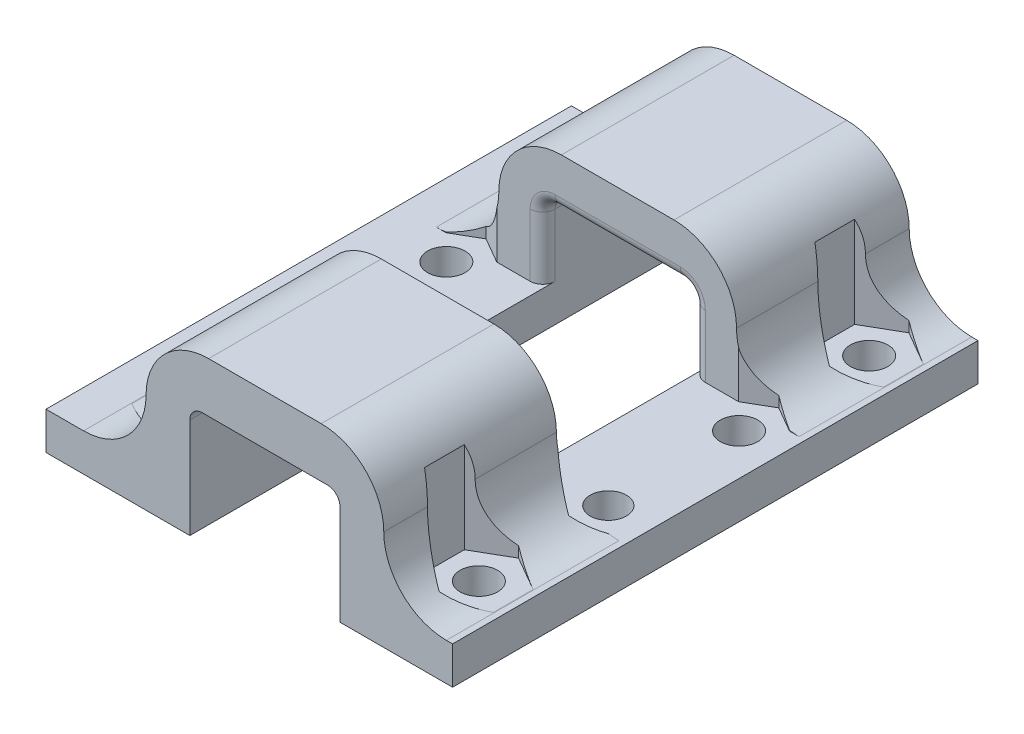
SolidWorks part; units mm, degrees
ref_plane "Спереди" through (0, 0, 0) normal (0, 0, 1) x (1, 0, 0)
ref_plane "Сверху" through (0, 0, 0) normal (0, 1, 0) x (1, 0, 0)
ref_plane "Справа" through (0, 0, 0) normal (1, 0, 0) x (0, 0, -1)
sketch "Эскиз2" plane through (0, 0, 0) normal (0, 1, 0) x (1, 0, 0)
  line L0 (-16.25, -21) -> (16.25, -21)
  line L1 (-16.25, -21) -> (-16.25, 21)
  line L2 (-16.25, 21) -> (16.25, 21)
  line L3 (16.25, -21) -> (16.25, 21)
  circle A0 centre (-10.45, -15.6) radius 1.5
  circle A1 centre (-10.45, -5.2) radius 1.5
  circle A2 centre (-10.45, 5.2) radius 1.5
  circle A3 centre (-10.45, 15.6) radius 1.5
  circle A4 centre (12.95, 15.6) radius 1.5
  circle A5 centre (12.95, 5.2) radius 1.5
  circle A6 centre (12.8998, -5.2) radius 1.4498
  circle A7 centre (12.95, -15.6) radius 1.5
extrude "Бобышка-Вытянуть1" add sketch "Эскиз2" along normal blind 3
sketch "Эскиз4" plane through (0, 3, 0) normal (0, 1, 0) x (1, 0, 0)
  line L0 (-10.45, 15.6) -> (12.95, 15.6) construction
  line L1 (1.25, 15.6) -> (1.25, -15.6) construction
  line L3 (-10.45, -15.6) -> (12.95, -15.6) construction
  line L4 (-16.25, -21) -> (16.25, -21) construction
  line L5 (-4.75, 21) -> (7.25, 21)
  line L6 (-4.75, 21) -> (-4.75, -21)
  line L7 (-4.75, -21) -> (7.25, -21)
  line L8 (7.25, 21) -> (7.25, -21)
  line L9 (-4.75, 21) -> (7.25, -21) construction
  line L10 (-4.75, -21) -> (7.25, 21) construction
  circle A0 centre (12.95, -15.6) radius 1.5 construction
  point P5 (1.25, 0)
  point P16 (11.45, -15.6)
  dimension "D1" = 12
extrude "Вырез-Вытянуть1" cut sketch "Эскиз4" against normal blind 22 contours L6 L5 L8 L7
sketch "Эскиз5" plane through (0, 0, 21) normal (0, 0, 1) x (1, 0, 0)
  line L0 (-16.25, 0) -> (-4.75, 0) construction
  line L2 (-4.75, 0) -> (-4.75, 3)
  line L4 (7.25, 0) -> (7.25, 3)
  line L6 (-4.75, 3) -> (-4.75, 9)
  line L7 (-4.75, 9) -> (7.25, 9)
  line L8 (7.25, 3) -> (7.25, 9)
  line L9 (-8.25, 0) -> (-4.75, 0)
  line L10 (-8.25, 0) -> (-8.25, 13)
  line L11 (-8.25, 13) -> (10.75, 13)
  line L12 (10.75, 0) -> (10.75, 13)
  line L13 (7.25, 0) -> (10.75, 0)
  dimension "D2" = 3.5
  dimension "D3" = 3.5
  dimension "D4" = 4
extrude "Бобышка-Вытянуть2" add sketch "Эскиз5" against normal up to surface (42 mm away) up to face at (11.75, 1.5, -21)
fillet "Скругление1" radius 5 4 edges at (-8.25, 13, 0) (10.75, 13, 0) (-8.25, 3, 0) (10.75, 3, 0)
sketch "Эскиз6" plane through (0, 13, 0) normal (0, 1, 0) x (1, 0, 0)
  line L0 (-3.25, 0) -> (5.75, 0) construction
  line L1 (-3.25, 21) -> (-3.25, -21) construction
  line L2 (5.75, -21) -> (5.75, 21) construction
  line L4 (-18.2884, -7.2) -> (18.2884, -7.2)
  line L5 (-18.2884, -7.2) -> (-18.2884, 7.2)
  line L6 (-18.2884, 7.2) -> (18.2884, 7.2)
  line L7 (18.2884, -7.2) -> (18.2884, 7.2)
  line L8 (-18.2884, -7.2) -> (18.2884, 7.2) construction
  line L9 (-18.2884, 7.2) -> (18.2884, -7.2) construction
  circle A0 centre (12.8998, -5.2) radius 1.4498 construction
  point P6 (0, 0)
  dimension "D1" = 2
extrude "Вырез-Вытянуть2" cut sketch "Эскиз6" against normal up to surface (10 mm away) up to face at (16, 3, 0)
fillet "Скругление2" radius 1 10 edges at (7.25, 6, 7.2) (7.25, 6, -7.2) (1.25, 9, 7.2) (1.25, 9, -7.2) (-4.75, 6, 7.2) (-4.75, 6, -7.2) (-4.75, 9, -14.1) (7.25, 9, -14.1) (7.25, 9, 14.1) (-4.75, 9, 14.1)
sketch "Эскиз7" plane through (0, 13, 0) normal (0, 1, 0) x (1, 0, 0)
  line L1 (-10.45, -12.4246) -> (-13.2, -14.0123)
  line L2 (-13.2, -14.0123) -> (-13.2, -17.1877)
  line L3 (-13.2, -17.1877) -> (-10.45, -18.7754)
  line L4 (-10.45, -18.7754) -> (-7.7, -17.1877)
  line L5 (-7.7, -17.1877) -> (-7.7, -14.0123)
  line L6 (-7.7, -14.0123) -> (-10.45, -12.4246)
  line L7 (12.95, -12.4246) -> (10.2, -14.0123)
  line L8 (10.2, -14.0123) -> (10.2, -17.1877)
  line L9 (10.2, -17.1877) -> (12.95, -18.7754)
  line L10 (12.95, -18.7754) -> (15.7, -17.1877)
  line L11 (15.7, -17.1877) -> (15.7, -14.0123)
  line L12 (15.7, -14.0123) -> (12.95, -12.4246)
  line L13 (-10.45, -8.3754) -> (-7.7, -6.7877)
  line L14 (-7.7, -6.7877) -> (-7.7, -3.6123)
  line L15 (-7.7, -3.6123) -> (-10.45, -2.0246)
  line L16 (-10.45, -2.0246) -> (-13.2, -3.6123)
  line L17 (-13.2, -3.6123) -> (-13.2, -6.7877)
  line L18 (-13.2, -6.7877) -> (-10.45, -8.3754)
  line L19 (-10.45, 2.0246) -> (-7.7, 3.6123)
  line L20 (-7.7, 3.6123) -> (-7.7, 6.7877)
  line L21 (-7.7, 6.7877) -> (-10.45, 8.3754)
  line L22 (-10.45, 8.3754) -> (-13.2, 6.7877)
  line L23 (-13.2, 6.7877) -> (-13.2, 3.6123)
  line L24 (-13.2, 3.6123) -> (-10.45, 2.0246)
  line L25 (-10.45, 12.4246) -> (-7.7, 14.0123)
  line L26 (-7.7, 14.0123) -> (-7.7, 17.1877)
  line L27 (-7.7, 17.1877) -> (-10.45, 18.7754)
  line L28 (-10.45, 18.7754) -> (-13.2, 17.1877)
  line L29 (-13.2, 17.1877) -> (-13.2, 14.0123)
  line L30 (-13.2, 14.0123) -> (-10.45, 12.4246)
  line L31 (12.8998, -8.3754) -> (15.6498, -6.7877)
  line L32 (15.6498, -6.7877) -> (15.6498, -3.6123)
  line L33 (15.6498, -3.6123) -> (12.8998, -2.0246)
  line L34 (12.8998, -2.0246) -> (10.1498, -3.6123)
  line L35 (10.1498, -3.6123) -> (10.1498, -6.7877)
  line L36 (10.1498, -6.7877) -> (12.8998, -8.3754)
  line L37 (12.95, 2.0246) -> (15.7, 3.6123)
  line L38 (15.7, 3.6123) -> (15.7, 6.7877)
  line L39 (15.7, 6.7877) -> (12.95, 8.3754)
  line L40 (12.95, 8.3754) -> (10.2, 6.7877)
  line L41 (10.2, 6.7877) -> (10.2, 3.6123)
  line L42 (10.2, 3.6123) -> (12.95, 2.0246)
  line L43 (12.95, 12.4246) -> (15.7, 14.0123)
  line L44 (15.7, 14.0123) -> (15.7, 17.1877)
  line L45 (15.7, 17.1877) -> (12.95, 18.7754)
  line L46 (12.95, 18.7754) -> (10.2, 17.1877)
  line L47 (10.2, 17.1877) -> (10.2, 14.0123)
  line L48 (10.2, 14.0123) -> (12.95, 12.4246)
  circle A0 centre (-10.45, -15.6) radius 2.75 construction
  circle A1 centre (12.95, -15.6) radius 2.75 construction
  circle A2 centre (-10.45, -5.2) radius 2.75 construction
  circle A3 centre (-10.45, 5.2) radius 2.75 construction
  circle A4 centre (-10.45, 15.6) radius 2.75 construction
  circle A5 centre (12.8998, -5.2) radius 2.75 construction
  circle A6 centre (12.95, 5.2) radius 2.75 construction
  circle A7 centre (12.95, 15.6) radius 2.75 construction
  dimension "D1" = 5.5
  dimension "D2" = 5.5
  dimension "D3" = 5.5
  dimension "D4" = 5.5
  dimension "D5" = 5.5
  dimension "D6" = 5.5
  dimension "D7" = 5.5
  dimension "D8" = 5.5
extrude "Вырез-Вытянуть3" cut sketch "Эскиз7" against normal up to surface (10 mm away) up to face at (12.6086, 3, 0)
